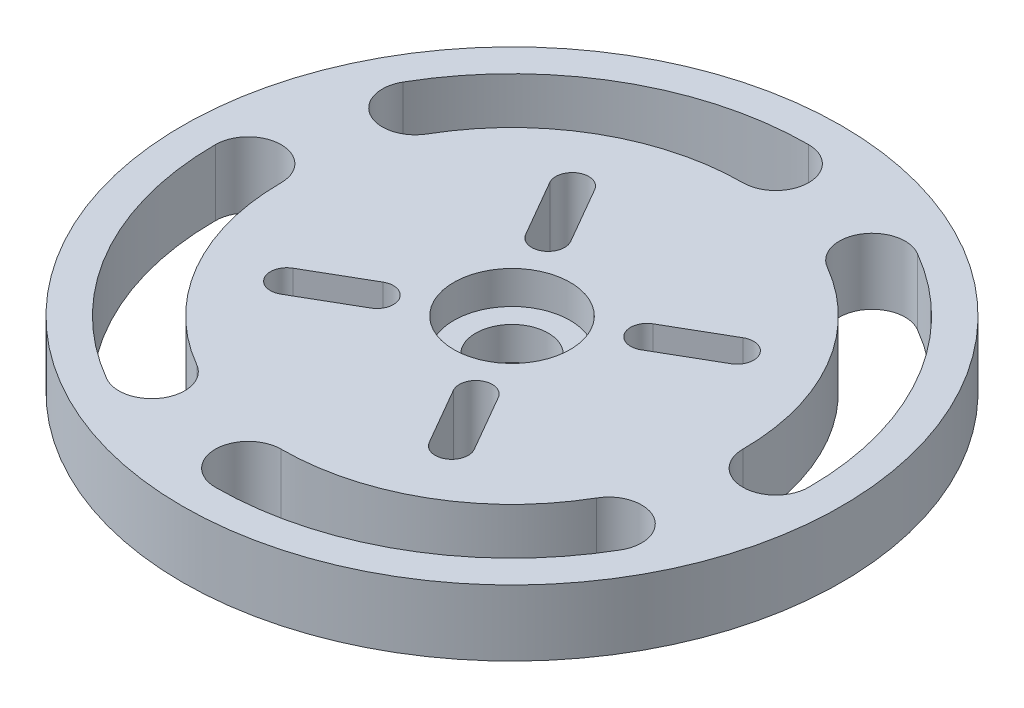
SolidWorks part; units mm, degrees
ref_plane "Front Plane" through (0, 0, 0) normal (0, 0, 1) x (1, 0, 0)
ref_plane "Top Plane" through (0, 0, 0) normal (0, 1, 0) x (1, 0, 0)
ref_plane "Right Plane" through (0, 0, 0) normal (1, 0, 0) x (0, 0, -1)
sketch "草图1" plane through (0, 0, 0) normal (0, 1, 0) x (1, 0, 0)
  circle A0 centre (0, 0) radius 1.65
  circle A1 centre (0, 0) radius 2.65
  circle A2 centre (0, 0) radius 15
  dimension "D1" = 3.3
  dimension "D2" = 5.3
  dimension "D3" = 30
extrude "凸台-拉伸2" add sketch "草图1" along normal blind 3 contours A2 A1 | A1 A0 | A0 region at (0, 0, 0) region at (-2.575, 0, 0) region at (-14.5757, 0, 0)
sketch "草图2" plane through (0, 3, 0) normal (0, 1, 0) x (1, 0, 0)
  line L0 (3.8967, 2.2508) -> (6.4944, 3.7513) construction
  line L3 (-2.2508, 3.8967) -> (-3.7513, 6.4944) construction
  line L6 (-2.9002, 3.5215) -> (-4.4008, 6.1193)
  line L7 (-1.6013, 4.2718) -> (-3.1019, 6.8696)
  line L8 (3.5215, 2.9002) -> (6.1193, 4.4008)
  line L9 (4.2718, 1.6013) -> (6.8696, 3.1019)
  line L10 (2.2508, -3.8967) -> (3.7513, -6.4944) construction
  line L11 (2.9002, -3.5215) -> (4.4008, -6.1193)
  line L12 (1.6013, -4.2718) -> (3.1019, -6.8696)
  line L13 (-3.8967, -2.2508) -> (-6.4944, -3.7513) construction
  line L14 (-3.5215, -2.9002) -> (-6.1193, -4.4008)
  line L15 (-4.2718, -1.6013) -> (-6.8696, -3.1019)
  circle A0 centre (0, 0) radius 1.65
  circle A1 centre (0, 0) radius 2.65
  arc A2 (0, 12.0047) -> (-10.3988, 5.9981) centre (0, 0) ccw construction
  arc A3 (0, 13.5047) -> (-11.6982, 6.7476) centre (0, 0) ccw
  arc A4 (0, 10.5047) -> (-9.0995, 5.2487) centre (0, 0) ccw
  arc A5 (0, 10.5047) -> (0, 13.5047) centre (0, 12.0047) ccw
  arc A6 (-11.6982, 6.7476) -> (-9.0995, 5.2487) centre (-10.3988, 5.9981) ccw
  arc A7 (12.0047, 0) -> (5.9981, 10.3988) centre (0, 0) ccw construction
  arc A12 (13.5047, 0) -> (6.7476, 11.6982) centre (0, 0) ccw
  arc A17 (10.5047, 0) -> (5.2487, 9.0995) centre (0, 0) ccw
  arc A18 (10.5047, 0) -> (13.5047, 0) centre (12.0047, 0) ccw
  arc A19 (6.7476, 11.6982) -> (5.2487, 9.0995) centre (5.9981, 10.3988) ccw
  arc A20 (0, -12.0047) -> (10.3988, -5.9981) centre (0, 0) ccw construction
  arc A21 (0, -13.5047) -> (11.6982, -6.7476) centre (0, 0) ccw
  arc A22 (0, -10.5047) -> (9.0995, -5.2487) centre (0, 0) ccw
  arc A23 (0, -10.5047) -> (0, -13.5047) centre (0, -12.0047) ccw
  arc A24 (11.6982, -6.7476) -> (9.0995, -5.2487) centre (10.3988, -5.9981) ccw
  arc A25 (-12.0047, 0) -> (-5.9981, -10.3988) centre (0, 0) ccw construction
  arc A26 (-13.5047, 0) -> (-6.7476, -11.6982) centre (0, 0) ccw
  arc A27 (-10.5047, 0) -> (-5.2487, -9.0995) centre (0, 0) ccw
  arc A28 (-10.5047, 0) -> (-13.5047, 0) centre (-12.0047, 0) ccw
  arc A29 (-6.7476, -11.6982) -> (-5.2487, -9.0995) centre (-5.9981, -10.3988) ccw
  arc A34 (-2.9002, 3.5215) -> (-1.6013, 4.2718) centre (-2.2508, 3.8967) ccw
  arc A35 (-3.1019, 6.8696) -> (-4.4008, 6.1193) centre (-3.7513, 6.4944) ccw
  arc A36 (3.5215, 2.9002) -> (4.2718, 1.6013) centre (3.8967, 2.2508) ccw
  arc A37 (6.8696, 3.1019) -> (6.1193, 4.4008) centre (6.4944, 3.7513) ccw
  arc A38 (2.9002, -3.5215) -> (1.6013, -4.2718) centre (2.2508, -3.8967) ccw
  arc A39 (3.1019, -6.8696) -> (4.4008, -6.1193) centre (3.7513, -6.4944) ccw
  arc A40 (-3.5215, -2.9002) -> (-4.2718, -1.6013) centre (-3.8967, -2.2508) ccw
  arc A41 (-6.8696, -3.1019) -> (-6.1193, -4.4008) centre (-6.4944, -3.7513) ccw
  point P6 (-6.0045, 10.3952)
  point P16 (10.3952, 6.0045)
  point P23 (6.0045, -10.3952)
  point P28 (0, 0)
  point P31 (-10.3952, -6.0045)
  point P36 (0, 0)
  point P38 (-3.0011, 5.1955)
  point P46 (5.1955, 3.0011)
  point P53 (3.0011, -5.1955)
  point P60 (-5.1955, -3.0011)
  point P65 (0, 0)
  dimension "D1" = 3.3
  dimension "D2" = 5.3
  dimension "D3" = 1.5
  dimension "D6" = 3
  dimension "D5" = 6
  dimension "D7" = 0.75
  dimension "D4" = 4
  dimension "D8" = 4
extrude "切除-拉伸2" cut sketch "草图2" against normal blind 17 contours A12 A19 A17 A18 | A21 A24 A22 A23 | A3 A6 A4 A5 | A0 | A26 A29 A27 A28 | L7 A35 L6 A34 | L15 A41 L14 A40 | L12 A39 L11 A38 | L9 A37 L8 A36 | A26 A29 A27 A28 region at (-3.0011, 3, -5.1955) region at (5.1955, 3, -3.0011) region at (3.0011, 3, 5.1955) region at (-5.1955, 3, 3.0011) region at (0, 3, 0) region at (-5.6493, 3, -9.7804) region at (9.7804, 3, -5.6493) region at (5.6493, 3, 9.7804) region at (-9.7804, 3, 5.6493)
extrude "切除-拉伸3" cut sketch "草图2<4>" against normal blind 1.5 contours A1 A0 region at (-2.575, 3, 0)
sketch "草图2<4>" plane through (0, 3, 0) normal (0, 1, 0) x (1, 0, 0) same geometry as "草图2"
